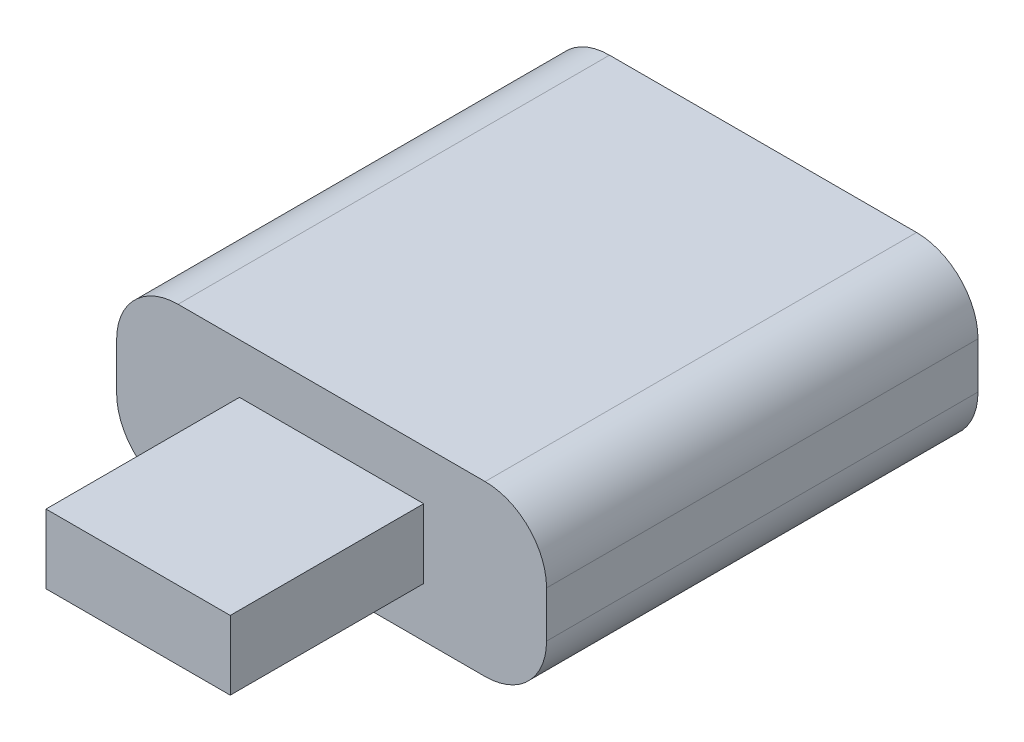
SolidWorks part; units mm, degrees
ref_plane "Front Plane" through (0, 0, 0) normal (0, 0, 1) x (1, 0, 0)
ref_plane "Top Plane" through (0, 0, 0) normal (0, 1, 0) x (1, 0, 0)
ref_plane "Right Plane" through (0, 0, 0) normal (1, 0, 0) x (0, 0, -1)
sketch "Sketch1" plane through (0, 0, 0) normal (0, 1, 0) x (1, 0, 0)
  line L1 (-14, 14.05) -> (14, 14.05)
  line L2 (-14, 14.05) -> (-14, -14.05)
  line L3 (-14, -14.05) -> (14, -14.05)
  line L4 (14, 14.05) -> (14, -14.05)
  line L5 (-14, 14.05) -> (14, -14.05) construction
  line L6 (-14, -14.05) -> (14, 14.05) construction
  line L7 (-6, -14.05) -> (6, -14.05)
  line L8 (-6, -14.05) -> (-6, -26.65)
  line L9 (-6, -26.65) -> (6, -26.65)
  line L10 (6, -14.05) -> (6, -26.65)
  point P0 (0, 0)
  point P11 (0, -26.65)
  dimension "D1" = 12
  dimension "D2" = 12.6
  dimension "D3" = 28.1
  dimension "D4" = 28
extrude "Boss-Extrude1" add sketch "Sketch1" along normal blind 5.5 and the other way blind 5.5 contours L4 L1 L2 L3 region at (0, 0, 0)
extrude "Boss-Extrude2" add sketch "Sketch1<4>" along normal blind 2.25 and the other way blind 2.25 contours L10 L3 L8 L9 region at (0, 0, 20.35)
sketch "Sketch1<4>" plane through (0, 0, 0) normal (0, 1, 0) x (1, 0, 0) same geometry as "Sketch1"
fillet "Fillet2" radius 4 4 edges at (-14, -5.5, 0) (-14, 5.5, 0) (14, -5.5, 0) (14, 5.5, 0)
